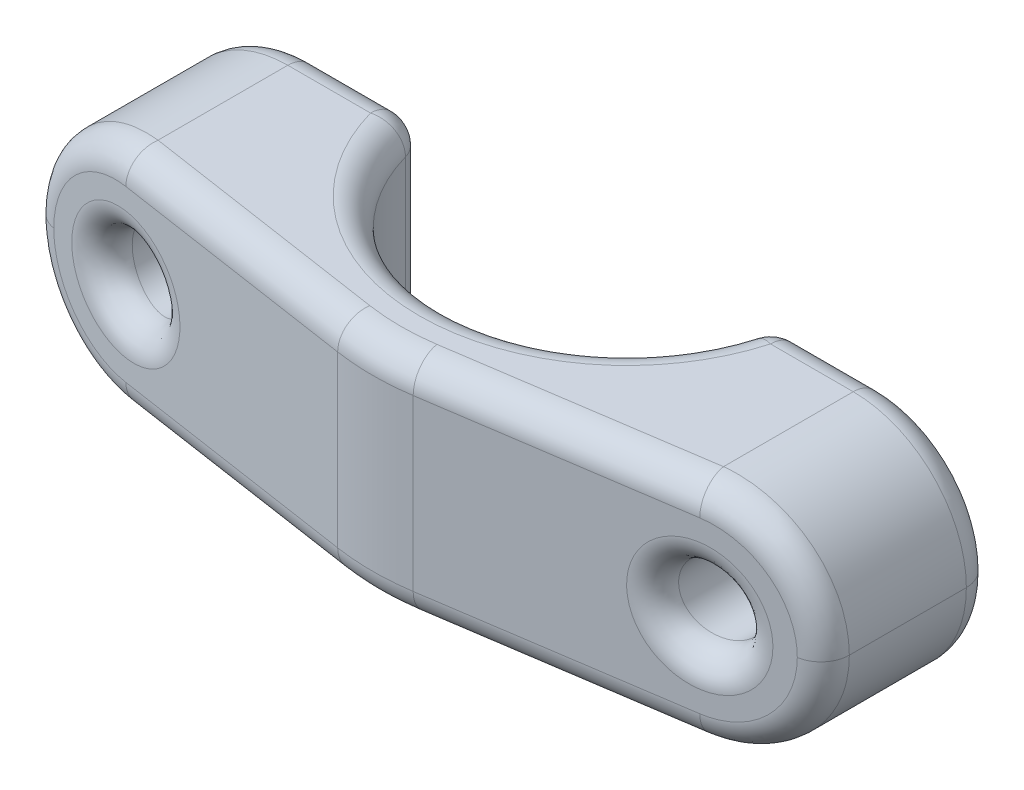
SolidWorks part; units mm, degrees
ref_plane "Спереди" through (0, 0, 0) normal (0, 0, 1) x (1, 0, 0)
ref_plane "Сверху" through (0, 0, 0) normal (0, 1, 0) x (1, 0, 0)
ref_plane "Справа" through (0, 0, 0) normal (1, 0, 0) x (0, 0, -1)
sketch "Эскиз1" plane through (0, 0, 0) normal (0, 1, 0) x (1, 0, 0)
  line L0 (-30.512, 0) -> (39.0104, 0) construction
  line L1 (0, 24.4199) -> (0, -24.9318) construction
  line L2 (-14, -1) -> (-6.2708, -1)
  line L3 (14, -1) -> (6.2708, -1)
  line L4 (-14, -1) -> (-14, -7)
  line L5 (14, -1) -> (14, -7)
  line L6 (-1.3355, -8.9004) -> (-14, -7)
  line L7 (1.3355, -8.9004) -> (14, -7)
  arc A0 (-6.2708, -1) -> (6.2708, -1) centre (0, 0) ccw
  arc A2 (-1.3355, -8.9004) -> (1.3355, -8.9004) centre (0, 0) ccw
  dimension "D1" = 6.35
  dimension "D2" = 9
  dimension "D3" = 1
  dimension "D4" = 14
  dimension "D5" = 6
extrude "Бобышка-Вытянуть1" add sketch "Эскиз1" along normal blind 8
sketch "Эскиз2" plane through (0, 0, 1) normal (0, 0, -1) x (-1, 0, 0)
  line L0 (-10, 4) -> (10, 4) construction
  line L1 (0, 13.0909) -> (0, -6.6646) construction
  circle A0 centre (-10, 4) radius 1.25
  circle A1 centre (10, 4) radius 1.25
  point P3 (0, 4)
  dimension "D3" = 2.5
  dimension "D1" = 4
  dimension "D2" = 20
extrude "Вырез-Вытянуть1" cut sketch "Эскиз2" against normal through all
fillet "Скругление1" radius 4 4 edges at (-14, 0, 4) (-14, 8, 4) (14, 0, 4) (14, 8, 4)
fillet "Скругление2" radius 1 24 edges at (-5.6678, 8, 8.2503) (0, 8, 9) (5.6678, 8, 8.2503) (12.8284, 6.8284, 7.1758) (12.8284, 1.1716, 7.1758) (5.6678, 0, 8.2503) (0, 0, 9) (-5.6678, 0, 8.2503) (-12.8284, 1.1716, 7.1758) (-8.1354, 0, 1) (-12.8284, 1.1716, 1) (-12.8284, 6.8284, 1) (8.1354, 0, 1) (12.8284, 1.1716, 1) (12.8284, 6.8284, 1) (11.25, 4, 7.4126) (-11.25, 4, 7.4126) (-12.8284, 6.8284, 7.1758) (6.2708, 4, 1) (-6.2708, 4, 1) (0, 0, 6.35) (0, 8, 6.35) (-8.1354, 8, 1) (8.1354, 8, 1)
